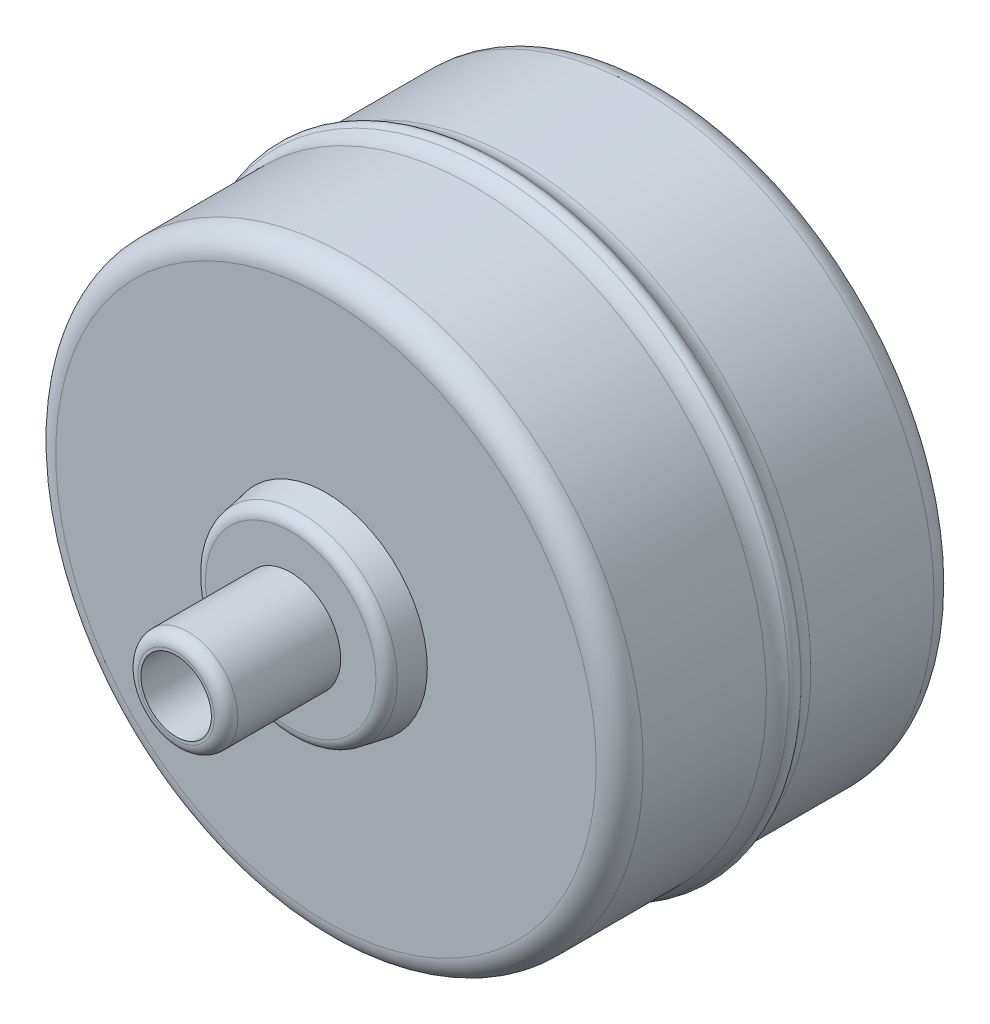
SolidWorks part; units mm, degrees
ref_plane "Alzado" through (0, 0, 0) normal (0, 0, 1) x (1, 0, 0)
ref_plane "Planta" through (0, 0, 0) normal (0, 1, 0) x (1, 0, 0)
ref_plane "Vista lateral" through (0, 0, 0) normal (1, 0, 0) x (0, 0, -1)
sketch "Croquis1" plane through (0, 0, 0) normal (0, 0, 1) x (1, 0, 0)
  circle A0 centre (0, 0) radius 25
  dimension "D1" = 50
extrude "Saliente-Extruir1" add sketch "Croquis1" along normal blind 28.75
sketch "Croquis2" plane through (0, 0, 0) normal (1, 0, 0) x (0, 0, -1)
  line L2 (-14.375, 25) -> (-14.375, -25) construction
  line L3 (0, 25) -> (-28.75, 25) construction
  line L4 (-28.75, -25) -> (0, -25) construction
  circle A0 centre (-14.375, 25) radius 0.75
  dimension "D1" = 1.5
ref_plane "Plano1" through (0, 0, 14.375) normal (0, 0, -1) x (-1, 0, 0)
sketch "Croquis3" plane through (0, 0, 14.375) normal (0, 0, -1) x (-1, 0, 0)
  circle A0 centre (0, 0) radius 25 construction
  circle A1 centre (0, 0) radius 25
sweep "Barrer1" add profiles "Croquis2" path "Croquis3"
fillet "Redondeo1" radius 2 2 edges at (25, 0, 13.625) (-25, 0, 15.125)
sketch "Croquis5" plane through (0, 0, 28.75) normal (0, 0, 1) x (1, 0, 0)
  circle A0 centre (0, 0) radius 4.25
  circle A1 centre (0, 0) radius 3
  dimension "D1" = 8.5
  dimension "D2" = 1.25
extrude "Saliente-Extruir2" add sketch "Croquis5" along normal blind 12.75
sketch "Croquis6" plane through (0, 0, 0) normal (0, 0, -1) x (-1, 0, 0)
  circle A0 centre (0, 0) radius 4
  circle A1 centre (0, 0) radius 3
  dimension "D1" = 8
  dimension "D2" = 1
extrude "Saliente-Extruir3" add sketch "Croquis6" along normal blind 13
sketch "Croquis7" plane through (0, 0, 28.75) normal (0, 0, 1) x (1, 0, 0)
  circle A0 centre (0, 0) radius 8.625
  dimension "D1" = 17.25
extrude "Saliente-Extruir4" add sketch "Croquis7" along normal blind 3
chamfer "Chaflán1" distance 3 angle 10 1 edges at (8.625, 0, 31.75) first distance on face at (8.625, 0, 31.75)
sketch "Croquis8" plane through (0, 0, 0) normal (0, 0, -1) x (-1, 0, 0)
  circle A0 centre (0, 0) radius 8.625 construction
  circle A1 centre (0, 0) radius 8.625
extrude "Saliente-Extruir5" add sketch "Croquis8" along normal blind 3
chamfer "Chaflán2" distance 3 angle 10 1 edges at (-8.625, 0, -3) first distance on face at (-8.625, 0, -3)
sketch "Croquis9" plane through (0, 0, 31.75) normal (0, 0, 1) x (1, 0, 0)
  circle A1 centre (0, 0) radius 3
  circle A2 centre (0, 0) radius 3
  dimension "D1" = 0
extrude "Cortar-Extruir1" cut sketch "Croquis9" against normal through all both and the other way through all
fillet "Redondeo2" radius 2 2 edges at (25, 0, 0) (25, 0, 28.75)
fillet "Redondeo3" radius 1 4 edges at (-8.096, 0, -3) (-4, 0, -13) (4.25, 0, 41.5) (8.096, 0, 31.75)
sketch "Croquis10" plane through (0, 0, 0) normal (0, 1, 0) x (1, 0, 0)
  line L0 (0, 0) -> (0, -28.75) construction
  line L1 (-8.625, -28.75) -> (8.625, -28.75) construction
  line L2 (0, -3) -> (21, -3)
  line L3 (23, -5) -> (23, -23.75)
  line L4 (21, -25.75) -> (0, -25.75)
  line L5 (0, -25.75) -> (0, -3)
  line L7 (23, 0) -> (-23, 0) construction
  arc A0 (23, -23.75) -> (21, -25.75) centre (21, -23.75) cw
  arc A1 (21, -3) -> (23, -5) centre (21, -5) cw
  point P7 (0, -6.2276)
  point P10 (0, -13.1739)
  point P13 (0, -14.375)
  point P18 (23, -25.75)
  dimension "D3" = 2
  dimension "D1" = 3
  dimension "D2" = 23
revolve "Cortar-Revolución1" cut sketch "Croquis10" angle 360 about L0
sketch "Croquis11" plane through (0, 0, 0) normal (0, 1, 0) x (1, 0, 0)
  line L0 (0, 0) -> (0, -28.75) construction
  line L1 (-8.625, -28.75) -> (8.625, -28.75) construction
  line L2 (0, -4.375) -> (22, -4.375)
  line L3 (22, -4.375) -> (22, -24.375)
  line L4 (22, -24.375) -> (0, -24.375)
  line L5 (0, -24.375) -> (0, -4.375)
  point P7 (0, -9.6505)
  point P10 (0, -14.375)
  point P11 (21.3219, -4.8013)
  dimension "D1" = 22
  dimension "D2" = 20
revolve "Revolución1" add sketch "Croquis11" angle 360 about L0
